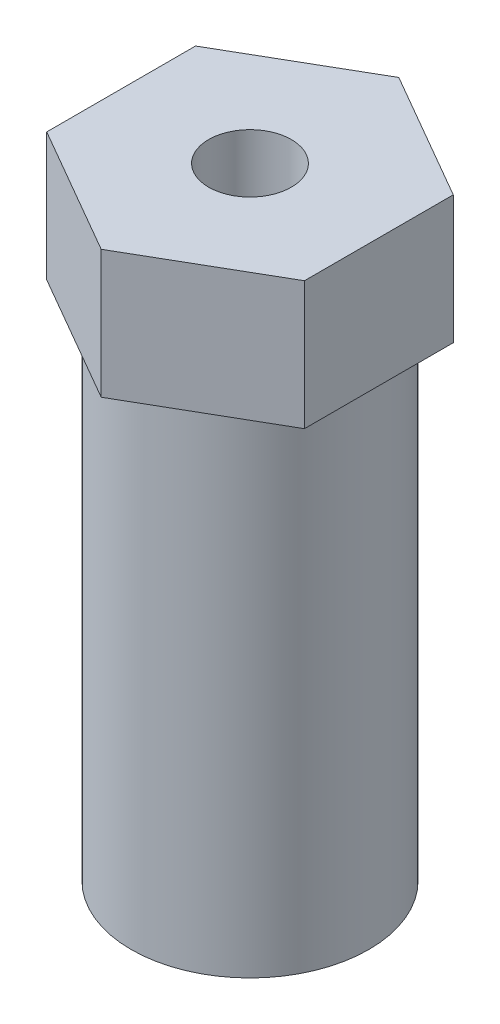
SolidWorks part; units mm, degrees
ref_plane "Front" through (0, 0, 0) normal (0, 0, 1) x (1, 0, 0)
ref_plane "Top" through (0, 0, 0) normal (0, 1, 0) x (1, 0, 0)
ref_plane "Right" through (0, 0, 0) normal (1, 0, 0) x (0, 0, -1)
sketch "Sketch1" plane through (0, 0, 0) normal (0, 1, 0) x (1, 0, 0)
  circle A0 centre (0, 0) radius 5.75
  dimension "D1" = 11.5
extrude "cylinderBase" add sketch "Sketch1" along normal blind 30.07
sketch "Sketch2" plane through (0, 30.07, 0) normal (0, 1, 0) x (1, 0, 0)
  circle A2 centre (0, 0) radius 3.34
  circle A3 centre (0, 0) radius 3.34
  dimension "D1" = 2.41
extrude "throughHole" cut sketch "Sketch2" against normal through all
sketch "Sketch3" plane through (0, 30.07, 0) normal (0, 1, 0) x (1, 0, 0)
  line L1 (0, -7.2) -> (6.2354, -3.6)
  line L2 (6.2354, -3.6) -> (6.2354, 3.6)
  line L3 (6.2354, 3.6) -> (0, 7.2)
  line L4 (0, 7.2) -> (-6.2354, 3.6)
  line L5 (-6.2354, 3.6) -> (-6.2354, -3.6)
  line L6 (-6.2354, -3.6) -> (0, -7.2)
  circle A0 centre (0, 0) radius 6.2354 construction
  point P1 (0, 7.2)
  dimension "D1" = 7.2
extrude "Boss-Extrude2" add sketch "Sketch3" against normal blind 6.2
sketch "Sketch4" plane through (0, 30.07, 0) normal (0, 1, 0) x (1, 0, 0)
  circle A0 centre (0, 0) radius 2
  dimension "D1" = 4
extrude "Cut-Extrude2" cut sketch "Sketch4" against normal through all
